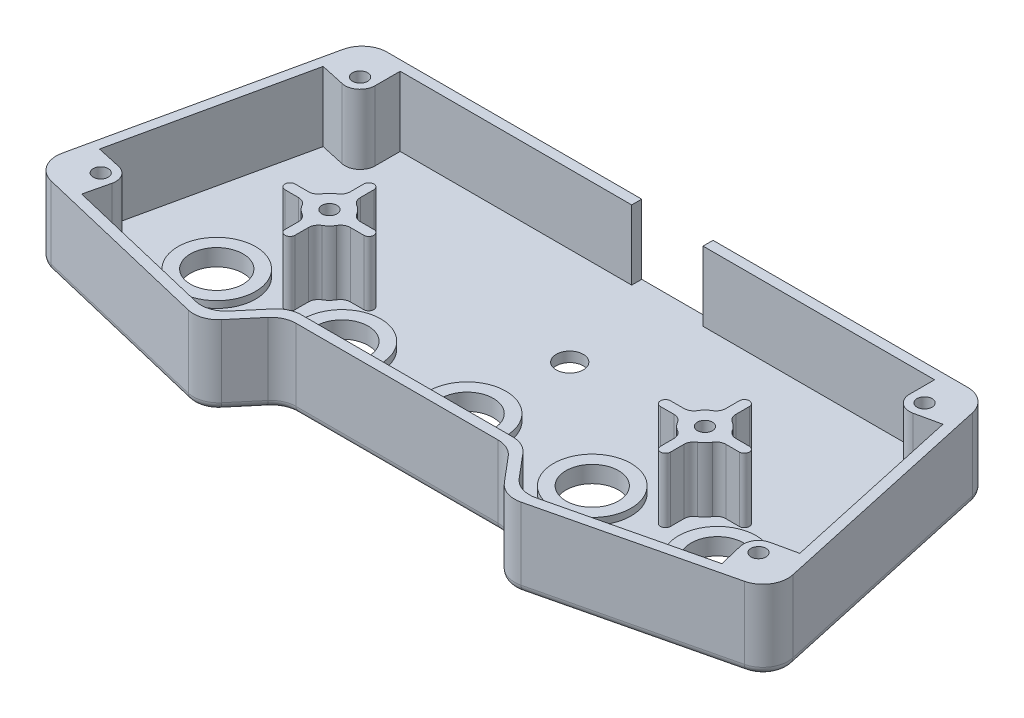
SolidWorks part; units mm, degrees
ref_plane "Front Plane" through (0, 0, 0) normal (0, 0, 1) x (1, 0, 0)
ref_plane "Top Plane" through (0, 0, 0) normal (0, 1, 0) x (1, 0, 0)
ref_plane "Right Plane" through (0, 0, 0) normal (1, 0, 0) x (0, 0, -1)
sketch "Sketch10" plane through (0, 0, 0) normal (0, 1, 0) x (1, 0, 0)
  line L0 (62, 32) -> (-62, 32)
  line L1 (-62, 32) -> (-74, -22.6992)
  line L2 (-74, -22.6992) -> (-30.236, -33.1736)
  line L3 (-30.236, -33.1736) -> (-22.5, -24)
  line L4 (-22.5, -24) -> (22.5, -24)
  line L5 (22.5, -24) -> (30.236, -33.1736)
  line L6 (30.236, -33.1736) -> (74, -22.6992)
  line L7 (74, -22.6992) -> (62, 32)
  line L8 (-50, -10) -> (-25, -10) construction
  line L9 (-25, -10) -> (0, -10) construction
  line L10 (0, -10) -> (25, -10) construction
  line L11 (25, -10) -> (50, -10) construction
  line L12 (-27, 0) -> (27, 0) construction
  line L13 (0, 0) -> (0, 32) construction
  line L14 (0, 0) -> (0, -24) construction
  line L15 (74, -22.6992) -> (22.5, -24) construction
  line L16 (-22.5, -24) -> (-74, -22.6992) construction
  circle A0 centre (50, -10) radius 5.25
  circle A2 centre (0, -10) radius 5.25
  circle A3 centre (25, -10) radius 5.25
  circle A5 centre (-50, -10) radius 5.25
  circle A6 centre (-25, -10) radius 5.25
  dimension "D1" = 10.5
  dimension "D2" = 25
  dimension "D3" = 56
  dimension "D4" = 124
  dimension "D5" = 10
  dimension "D6" = 148
  dimension "D7" = 56
  dimension "D8" = 45
  dimension "D9" = 32
  dimension "D10" = 45
  dimension "D11" = 12
extrude "Boss-Extrude5" add sketch "Sketch10" along normal blind 2 separate body
sketch "Sketch11" plane through (0, 2, 0) normal (0, 1, 0) x (1, 0, 0)
  line L0 (-74, -22.6992) -> (-62, 32)
  line L1 (-62, 32) -> (62, 32)
  line L2 (62, 32) -> (74, -22.6992)
  line L3 (74, -22.6992) -> (30.236, -33.1736)
  line L4 (30.236, -33.1736) -> (22.5, -24)
  line L5 (22.5, -24) -> (-22.5, -24)
  line L6 (-22.5, -24) -> (-30.236, -33.1736)
  line L7 (-30.236, -33.1736) -> (-74, -22.6992)
  line L8 (-30.9699, -30.9414) -> (-71.6259, -21.2109)
  line L9 (-71.6259, -21.2109) -> (-60.3912, 30)
  line L10 (-60.3912, 30) -> (60.3912, 30)
  line L11 (60.3912, 30) -> (71.6259, -21.2109)
  line L12 (71.6259, -21.2109) -> (30.9699, -30.9414)
  line L13 (30.9699, -30.9414) -> (23.4296, -22)
  line L14 (23.4296, -22) -> (-23.4296, -22)
  line L15 (-23.4296, -22) -> (-30.9699, -30.9414)
  dimension "D1" = 2
extrude "Boss-Extrude7" add sketch "Sketch11" along direction (0, -1, 0) on the side of the normal offset from surface (13.875 mm away) 15.875 up to face at (-50, 0, 15.25)
fillet "Fillet4" radius 5 16 edges at (62, 7.9375, -32) (74, 7.9375, 22.6992) (30.236, 7.9375, 33.1736) (22.5, 7.9375, 24) (-22.5, 7.9375, 24) (-30.236, 7.9375, 33.1736) (-62, 7.9375, -32) (-74, 7.9375, 22.6992) (71.6259, 8.9375, 21.2109) (60.3912, 8.9375, -30) (30.9699, 8.9375, 30.9414) (23.4296, 8.9375, 22) (-23.4296, 8.9375, 22) (-30.9699, 8.9375, 30.9414) (-71.6259, 8.9375, 21.2109) (-60.3912, 8.9375, -30)
fillet "Fillet5" radius 1.5 16 edges at (30.509, 0, 32.3431) (26.1233, 0, 28.2966) (22.2835, 0, 24.4659) (0, 0, 24) (-22.2835, 0, 24.4659) (-26.1233, 0, 28.2966) (-30.509, 0, 32.3431) (-51.2316, 0, 28.1485) (-72.3012, 0, 21.6342) (-67.9053, 0, -5.0822) (-61.1119, 0, -30.896) (0, 0, -32) (61.1119, 0, -30.896) (67.9053, 0, -5.0822) (72.3012, 0, 21.6342) (51.2316, 0, 28.1485)
sketch "Sketch12" plane through (0, 2, 0) normal (0, 1, 0) x (1, 0, 0)
  line L0 (-61.8959, 23.1411) -> (-57.0121, 22.0697)
  line L1 (-61.2531, 26.0714) -> (-70.5746, -16.4188) construction
  line L2 (-53.3692, 25) -> (-53.3692, 30)
  line L3 (56.3692, 30) -> (-56.3692, 30) construction
  line L4 (-53.3692, 30) -> (-56.3692, 30)
  line L5 (-61.2531, 26.0714) -> (-61.8959, 23.1411)
  line L6 (-70.5746, -16.4188) -> (-69.9318, -13.4885)
  line L7 (-69.9318, -13.4885) -> (-65.0479, -14.5599)
  line L8 (-62.7732, -18.1885) -> (-63.937, -23.0512)
  line L9 (-66.8546, -22.3529) -> (-33.9684, -30.2238) construction
  line L10 (-63.937, -23.0512) -> (-66.8546, -22.3529)
  line L11 (0, 0) -> (0, 17.9434) construction
  line L12 (63.937, -23.0512) -> (66.8546, -22.3529)
  line L13 (62.7732, -18.1885) -> (63.937, -23.0512)
  line L14 (69.9318, -13.4885) -> (65.0479, -14.5599)
  line L15 (70.5746, -16.4188) -> (69.9318, -13.4885)
  line L16 (61.2531, 26.0714) -> (61.8959, 23.1411)
  line L17 (53.3692, 30) -> (56.3692, 30)
  line L18 (53.3692, 25) -> (53.3692, 30)
  line L19 (61.8959, 23.1411) -> (57.0121, 22.0697)
  arc A0 (-57.0121, 22.0697) -> (-53.3692, 25) centre (-56.3692, 25) ccw
  arc A1 (-56.3692, 30) -> (-61.2531, 26.0714) centre (-56.3692, 25) ccw
  arc A2 (-65.0479, -14.5599) -> (-62.7732, -18.1885) centre (-65.6908, -17.4902) cw
  arc A3 (-66.8546, -22.3529) -> (-70.5746, -16.4188) centre (-65.6908, -17.4902) cw
  circle A4 centre (-56.3692, 25) radius 1.5
  circle A5 centre (-65.6908, -17.4902) radius 1.5
  circle A6 centre (65.6908, -17.4902) radius 1.5
  circle A7 centre (56.3692, 25) radius 1.5
  arc A8 (66.8546, -22.3529) -> (70.5746, -16.4188) centre (65.6908, -17.4902) ccw
  arc A9 (65.0479, -14.5599) -> (62.7732, -18.1885) centre (65.6908, -17.4902) ccw
  arc A10 (56.3692, 30) -> (61.2531, 26.0714) centre (56.3692, 25) cw
  arc A11 (57.0121, 22.0697) -> (53.3692, 25) centre (56.3692, 25) cw
  dimension "D1" = 3
  dimension "D2" = 1.5
extrude "Boss-Extrude8" add sketch "Sketch12" along normal up to surface (13.875 mm away) up to face at (0, 15.875, 10.9337)
sketch "Sketch14" plane through (0, 0, -30) normal (0, 0, 1) x (1, 0, 0)
  line L0 (-53.3692, 15.875) -> (53.3692, 15.875) construction
  line L5 (0, 0) -> (0, 15.875) construction
  line L10 (-6.625, 15.03) -> (-6.625, 2.5) construction
  line L11 (-7.125, 15.875) -> (7.125, 15.875)
  line L12 (-7.125, 15.875) -> (-7.125, 2)
  line L13 (-7.125, 2) -> (7.125, 2)
  line L14 (7.125, 15.875) -> (7.125, 2)
  line L15 (53.3692, 2) -> (-53.3692, 2) construction
  dimension "D1" = 0.5
extrude "Cut-Extrude2" cut sketch "Sketch14" against normal through all
sketch "Sketch15" plane through (0, 0, 0) normal (0, -1, 0) x (1, 0, 0)
  line L0 (0, -10.5) -> (0, -30.5) construction
  line L1 (-57.978, -30.5) -> (57.978, -30.5) construction
  circle A0 centre (0, -10.5) radius 2.7
  dimension "D2" = 5.4
  dimension "D1" = 20
extrude "Cut-Extrude3" cut sketch "Sketch15" against normal through all contours A0
sketch "Sketch16" plane through (0, 2, 0) normal (0, 1, 0) x (1, 0, 0)
  circle A0 centre (25, -10) radius 7.75
  circle A1 centre (25, -10) radius 5.25
  circle A2 centre (0, -10) radius 7.75
  circle A3 centre (0, -10) radius 5.25
  circle A4 centre (-50, -10) radius 5.25
  circle A5 centre (-50, -10) radius 7.75
  circle A6 centre (-25, -10) radius 5.25
  circle A7 centre (-25, -10) radius 7.75
  circle A9 centre (-50, -10) radius 5.25 construction
  circle A10 centre (-25, -10) radius 5.25 construction
  circle A12 centre (25, -10) radius 5.25 construction
  circle A13 centre (0, -10) radius 5.25 construction
  circle A14 centre (50, -10) radius 7.75
  circle A15 centre (50, -10) radius 5.25
  circle A16 centre (50, -10) radius 5.25 construction
  dimension "D1" = 2.5
extrude "Boss-Extrude9" add sketch "Sketch16" along normal blind 1.35
sketch "Sketch17" plane through (0, 2, 0) normal (0, 1, 0) x (1, 0, 0)
  line L0 (-38.5, 3.873) -> (-38.5, 7.873)
  line L3 (-36.5, 7.873) -> (-36.5, 3.873)
  line L4 (-33.627, 1) -> (-29.627, 1)
  line L5 (-29.627, -1) -> (-33.627, -1)
  line L8 (-41.373, -1) -> (-45.373, -1)
  line L9 (-45.373, 1) -> (-41.373, 1)
  line L10 (-45.373, 0) -> (-37.5, 0) construction
  line L11 (-37.5, 0) -> (-29.627, 0) construction
  line L12 (-37.5, -1.5) -> (-37.5, 0) construction
  line L13 (-37.5, 7.873) -> (-37.5, 0) construction
  line L14 (-38.5, -3.873) -> (-38.5, -7.873)
  line L15 (-37.5, 0) -> (0, 0) construction
  line L16 (-36.5, -7.873) -> (-36.5, -3.873)
  line L17 (-37.5, -7.873) -> (-37.5, 0) construction
  arc A0 (-38.5, 3.873) -> (-41.373, 1) centre (-37.5, 0) ccw
  arc A3 (-38.5, 7.873) -> (-36.5, 7.873) centre (-37.5, 7.873) cw
  arc A4 (-29.627, 1) -> (-29.627, -1) centre (-29.627, 0) cw
  arc A6 (-45.373, -1) -> (-45.373, 1) centre (-45.373, 0) cw
  arc A7 (-33.627, 1) -> (-36.5, 3.873) centre (-37.5, 0) ccw
  arc A8 (-41.373, -1) -> (-38.5, -3.873) centre (-37.5, 0) ccw
  circle A10 centre (-37.5, 0) radius 1.5
  arc A11 (-38.5, -7.873) -> (-36.5, -7.873) centre (-37.5, -7.873) ccw
  arc A12 (-36.5, -3.873) -> (-33.627, -1) centre (-37.5, 0) ccw
  dimension "D1" = 37.5
  dimension "D4" = 8
  dimension "D5" = 3
  dimension "D2" = 2
  dimension "D3" = 4
extrude "PCB Mount Posts" add sketch "Sketch17" along normal offset from surface (12.875 mm away) 1 up to face at (0, 15.875, 4.8751)
fillet "Fillet6" radius 2 8 edges at (-41.373, 8.4375, -1) (-38.5, 8.4375, -3.873) (-36.5, 8.4375, -3.873) (-33.627, 8.4375, -1) (-33.627, 8.4375, 1) (-36.5, 8.4375, 3.873) (-38.5, 8.4375, 3.873) (-41.373, 8.4375, 1)
mirror "Mirror1" about plane through (0, 0, 0) normal (1, 0, 0) of "Fillet6", "Boss-Extrude9", "PCB Mount Posts"
sketch "Sketch18" plane through (0, 0, 0) normal (0, -1, 0) x (1, 0, 0)
  line L0 (44.9872, 5.1655) -> (29.1689, -28.757) construction
  line L1 (50, 10) -> (47.253, 4.109) construction
  line L2 (44.9872, 5.1655) -> (37.0218, 5.1655) construction
  line L3 (47.253, 4.109) -> (44.9872, 5.1655) construction
  circle A1 centre (50, 10) radius 5.25 construction
  text T0 "PENALTY" font "Arial" height 5
  point P5 (52.0733, 2.4723)
  point P6 (0, 0)
  point P10 (50, 0.8267)
  point P11 (47.4616, 4.386)
  dimension "D1" = 65
  dimension "D2" = 2.5
  dimension "D3" = 6.5
sketch "Sketch19" plane through (0, 0, 0) normal (0, -1, 0) x (1, 0, 0)
  line L1 (25, 10) -> (22.4643, 4.5622) construction
  line L3 (22.4643, 4.5622) -> (7.2365, -28.0939) construction
  line L4 (22.4643, 4.5622) -> (16.5733, 7.3092) construction
  line L5 (16.5733, 7.3092) -> (0.4087, -27.3558) construction
  line L6 (16.5733, 7.3092) -> (12.5836, 7.3092) construction
  circle A1 centre (25, 10) radius 5.25 construction
  text T0 "START/" font "Arial" height 5
  text T1 "RESUME" font "Arial" height 5
  point P10 (23.5272, 4.1067)
  point P11 (26.4604, 1.0439)
  point P12 (26.0661, -0.2721)
  point P13 (26.4825, 0.9084)
  dimension "D1" = 6.5
  dimension "D2" = 65
extrude "Penalty Left" cut sketch "Sketch18" against normal blind 0.5
sketch "Sketch20" plane through (0, 0, 0) normal (0, -1, 0) x (1, 0, 0)
  line L0 (12.7379, 4) -> (-12.7379, 4) construction
  line L1 (0, 10) -> (0, 4) construction
  circle A0 centre (0, 10) radius 5.25 construction
  text T0 "RESET\r\n" font "Arial" height 5
  point P4 (12.7379, 0.7445)
sketch "Sketch21" plane through (0, 0, 0) normal (0, -1, 0) x (1, 0, 0)
  line L0 (-9.8018, -16.6771) -> (-20.1985, 5.6187) construction
  line L1 (-20.1985, 5.6187) -> (-22.4643, 4.5622) construction
  line L2 (-20.1985, 5.6187) -> (-17.3887, 5.6187) construction
  line L3 (-22.4643, 4.5622) -> (-25, 10) construction
  circle A0 centre (-25, 10) radius 5.25 construction
  text T0 "PAUSE" font "Arial" height 5
  point P1 (0, 0)
  point P7 (-22.1901, 0.8701)
  dimension "D1" = 65
  dimension "D2" = 2.5
sketch "Sketch22" plane through (0, 0, 0) normal (0, -1, 0) x (1, 0, 0)
  line L0 (-28.1093, -31.0293) -> (-45.1985, 5.6187) construction
  line L1 (-45.1985, 5.6187) -> (-47.4643, 4.5622) construction
  line L2 (-45.1985, 5.6187) -> (-39.847, 5.6187) construction
  line L3 (-47.4643, 4.5622) -> (-50, 10) construction
  circle A0 centre (-50, 10) radius 5.25 construction
  text T0 "PENALTY" font "Arial" height 5
  point P4 (0, 0)
  point P9 (0, 0)
  point P10 (-24.6166, -28.9653)
  dimension "D1" = 65
  dimension "D3" = 2.5
extrude "Start" cut sketch "Sketch19" against normal blind 0.5
extrude "Reset" cut sketch "Sketch20" against normal blind 0.5
extrude "Pause" cut sketch "Sketch21" against normal blind 0.5
extrude "Penalty R" cut sketch "Sketch22" against normal blind 0.5
equation "\"TextAngle\"= 65"
equation "\"D1@Sketch18\"=\"TextAngle\""
equation "\"D1@Sketch21\"=\"TextAngle\""
equation "\"D1@Sketch22\"=\"TextAngle\""
equation "\"TextFromCircle\"=6"
equation "\"D2@Sketch19\"=\"TextAngle\""
equation "\"D3@Sketch19\"=\"TextFromCircle\""
equation "\"D1@Sketch20\"=\"TextFromCircle\""
equation "\"D3@Sketch21\"=\"TextFromCircle\""
equation "\"D2@Sketch22\"=\"TextFromCircle\""
